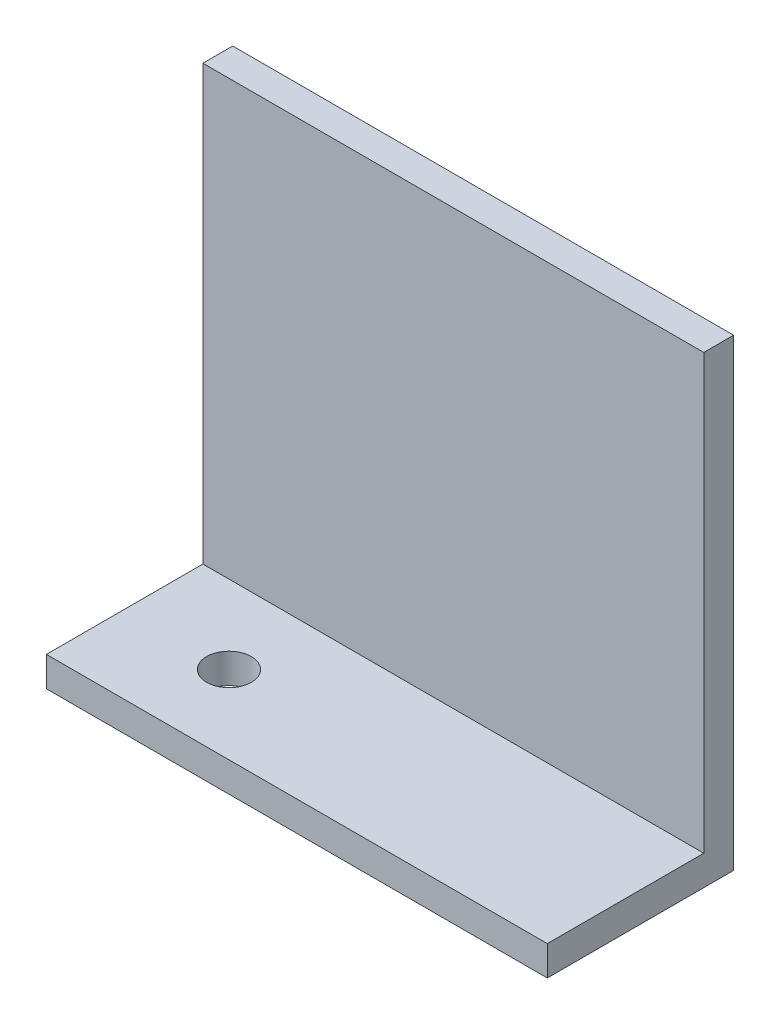
SolidWorks part; units mm, degrees
ref_plane "Front Plane" through (0, 0, 0) normal (0, 0, 1) x (1, 0, 0)
ref_plane "Top Plane" through (0, 0, 0) normal (0, 1, 0) x (1, 0, 0)
ref_plane "Right Plane" through (0, 0, 0) normal (1, 0, 0) x (0, 0, -1)
sketch "Sketch1" plane through (0, 0, 0) normal (0, 1, 0) x (1, 0, 0)
  line L1 (0, 0) -> (33.6093, 0)
  line L2 (0, 0) -> (0, 12.5)
  line L3 (0, 12.5) -> (33.6093, 12.5)
  line L4 (33.6093, 0) -> (33.6093, 12.5)
  dimension "D1" = 12.5
extrude "Boss-Extrude1" add sketch "Sketch1" along normal blind 2
sketch "Sketch2" plane through (0, 0, -12.5) normal (0, 0, -1) x (-1, 0, 0)
  line L1 (-33.6093, 2) -> (0, 2)
  line L2 (-33.6093, 2) -> (-33.6093, 31.1024)
  line L3 (-33.6093, 31.1024) -> (0, 31.1024)
  line L4 (0, 2) -> (0, 31.1024)
extrude "Boss-Extrude2" add sketch "Sketch2" against normal blind 2
sketch "Sketch3" plane through (0, 2, 0) normal (0, 1, 0) x (1, 0, 0)
  line L0 (0, 5.25) -> (33.6093, 5.25) construction
  line L1 (0, 10.5) -> (0, 0) construction
  line L2 (33.6093, 0) -> (33.6093, 10.5) construction
  circle A0 centre (7, 5.25) radius 1.5
  dimension "D1" = 3
  dimension "D2" = 5.5
extrude "Cut-Extrude1" cut sketch "Sketch3" against normal blind 2 contours A0
